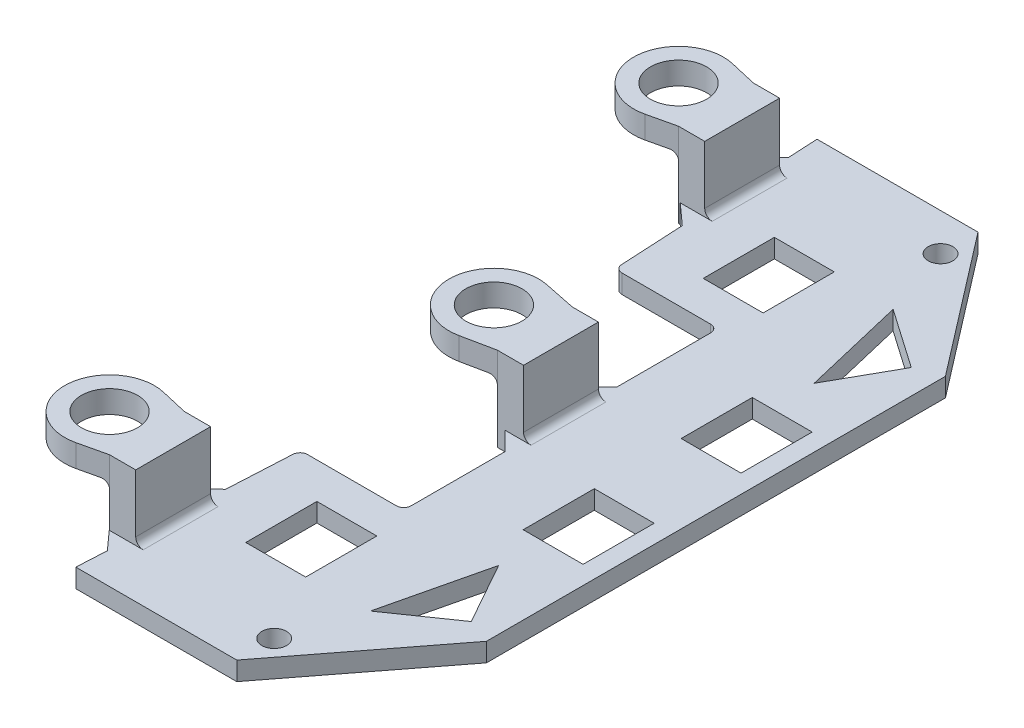
SolidWorks part; units mm, degrees
ref_plane "Plano frontal" through (0, 0, 0) normal (0, 0, 1) x (1, 0, 0)
ref_plane "Plano superior" through (0, 0, 0) normal (0, 1, 0) x (1, 0, 0)
ref_plane "Plano direito" through (0, 0, 0) normal (1, 0, 0) x (0, 0, -1)
sketch "Esboço1" plane through (0, 0, 0) normal (0, 1, 0) x (1, 0, 0)
  line L2 (-10.5, -21) -> (-10.5, 21) construction
  line L15 (-10.5, 21) -> (-10.5, -21)
  line L24 (-25.8, -49.5) -> (-4.3, -49.5)
  line L27 (-25.8, 49.5) -> (-4.3, 49.5)
  line L28 (-4.3, 49.5) -> (10.2, 30.65)
  line L29 (10.2, 30.65) -> (10.2, -30.65)
  line L30 (10.2, -30.65) -> (-4.3, -49.5)
  line L32 (-10.5, -21) -> (-24.3, -21)
  line L33 (-24.3, -21) -> (-25.8, -49.5)
  line L34 (-10.5, 21) -> (-24.3, 21)
  line L35 (-24.3, 21) -> (-25.8, 49.5)
  point P0 (0, 0)
  point P1 (0, 0)
  point P2 (0, 0)
  point P3 (-10.5, 0)
  dimension "D3" = 10.5
  dimension "D4" = 36
  dimension "D2" = 10.2
  dimension "D5" = 34.5
  dimension "D6" = 14.5
  dimension "D7" = 42
  dimension "D11" = 49.5
  dimension "D13" = 49.5
  dimension "D14" = 30.65
  dimension "D15" = 30.65
  dimension "D16" = 21.5
extrude "Ressalto-extrusão1" add sketch "Esboço1" along normal mid plane 2.5 contours L24 L30 L29 L28 L27 | L15 | L35 L34 L15 | L24 L30 L29 L28 L27 L35 L34 L15 L32 L33 region at (-6.3414, 0, 0)
sketch "Esboço8" plane through (0, 1.25, 0) normal (0, 1, 0) x (1, 0, 0)
  line L1 (-17.3, 25.8) -> (-9.3, 25.8)
  line L2 (-17.3, 25.8) -> (-17.3, 35.3)
  line L3 (-17.3, 35.3) -> (-9.3, 35.3)
  line L4 (-9.3, 25.8) -> (-9.3, 35.3)
  line L6 (-25.8, 49.5) -> (-4.3, 49.5) construction
  line L7 (10.2, 30.65) -> (10.2, -30.65) construction
  line L8 (-0.25, 5.8) -> (7.75, 5.8)
  line L9 (-0.25, 5.8) -> (-0.25, 15.3)
  line L10 (-0.25, 15.3) -> (7.75, 15.3)
  line L11 (7.75, 5.8) -> (7.75, 15.3)
  line L12 (-4.3, 49.5) -> (10.2, 30.65) construction
  line L13 (-4.3, 44.5) -> (-8.1462, 49.5) construction
  line L14 (-1.375, 0) -> (1.375, 0) construction
  circle A0 centre (-4.3, 44.5) radius 1.65
  point P6 (-13.3, 25.8)
  point P19 (-0.25, 10.55)
  point P23 (-17.3, 30.55)
  point P24 (3.75, 15.3)
  dimension "D8" = 3.3
  dimension "D1" = 8
  dimension "D2" = 9.5
  dimension "D3" = 23.7
  dimension "D4" = 23.5
  dimension "D5" = 15.3
  dimension "D6" = 2.45
  dimension "D7" = 3.0486
  dimension "D9" = 6.3082
  dimension "D10" = 14.5
  dimension "D11" = 5
  dimension "D12" = 10.55
  dimension "D13" = 30.55
  dimension "D14" = 6.45
extrude "Corte-extrusão6" cut sketch "Esboço8" against normal through all
sketch "Esboço9" plane through (0, 1.25, 0) normal (0, 1, 0) x (1, 0, 0)
  line L0 (6.9015, 29.3849) -> (-1.0461, 34.9078)
  line L1 (-1.0461, 34.9078) -> (2.2431, 21.0714)
  line L2 (2.2431, 21.0714) -> (6.9015, 29.3849)
  point P2 (-7.0972, -44.8275)
  point P4 (2.2431, 21.0714)
  point P5 (-1.0461, 34.9078)
  point P6 (-2.3014, -31.2953)
  point P7 (-1.2891, -41.9419)
  point P8 (-0.6864, -30.8137)
  point P9 (-2.4256, 37.7818)
  point P10 (6.9015, 29.3849)
  point P11 (2.6327, -36.8446)
extrude "Corte-extrusão5" cut sketch "Esboço9" against normal blind 10
sketch "Esboço12" plane through (0, 0, 0) normal (0, 1, 0) x (1, 0, 0)
  line L1 (-24.3, 43) -> (-27.8, 43)
  line L2 (-24.3, 43) -> (-24.3, 33)
  line L3 (-24.3, 33) -> (-27.8, 33)
  line L4 (-27.8, 43) -> (-27.8, 33)
  line L5 (10.2, 30.65) -> (10.2, -30.65) construction
  point P4 (-24.3, 38)
  point P6 (-26.05, 33)
  dimension "D2" = 3.5
  dimension "D1" = 38
  dimension "D3" = 10
  dimension "D4" = 36.25
extrude "Ressalto-extrusão4" add sketch "Esboço12" along normal blind 10 and the other way blind 1.25
sketch "Esboço13" plane through (0, 10, 0) normal (0, 1, 0) x (1, 0, 0)
  line L0 (-27.8, 43) -> (-27.8, 33) construction
  line L1 (10.2, 30.65) -> (10.2, -30.65) construction
  line L2 (-31.445, 43.845) -> (-27.8, 43)
  line L3 (-27.8, 43) -> (-27.8, 33)
  line L4 (-27.8, 33) -> (-31.445, 32.155)
  circle A0 centre (-32.8, 38) radius 6 construction
  arc A1 (-31.445, 43.845) -> (-31.445, 32.155) centre (-32.8, 38) ccw
  circle A2 centre (-32.8, 38) radius 3.75
  point P5 (-27.8, 38)
  point P13 (0, 0)
  line M4 (-27.8, 43) -> (-27.8, 33)
  dimension "D2" = 12
  dimension "D4" = 7.5
  dimension "D3" = 43
extrude "Ressalto-extrusão5" add sketch "Esboço13" against normal blind 3 contours L2 A1 L4 M4 region at (-29.6593, 10, -43.2639)
sketch "Esboço11" [suppressed] plane through (0, 0.9, 0) normal (0, 1, 0) x (1, 0, 0)
  circle A2 centre (-28.61, -38) radius 1.75
  circle A3 centre (-28.61, -38) radius 1.75 construction
  circle A4 centre (-28.61, -38) radius 2.5
  dimension "D1" = 5
extrude "Ressalto-extrusão3" [suppressed] add sketch "Esboço11" along normal blind 1.5
mirror "Espelhar1" about plane through (0, 0, 0) normal (0, 0, 1) of "Ressalto-extrusão5", "Ressalto-extrusão4", "Corte-extrusão6", "Corte-extrusão5"
sketch "Esboço14" plane through (0, -1.25, 0) normal (0, -1, 0) x (1, 0, 0)
  line L0 (1.375, 0) -> (-1.375, 0) construction
  line L1 (-10.5, -5) -> (-14, -5)
  line L2 (-10.5, -5) -> (-10.5, 5)
  line L3 (-10.5, 5) -> (-14, 5)
  line L4 (-14, -5) -> (-14, 5)
  line L5 (-10.5, -21) -> (-10.5, 21) construction
  point P4 (-10.5, 0)
  dimension "D1" = 10
  dimension "D2" = 3.5
extrude "Ressalto-extrusão6" add sketch "Esboço14" against normal up to surface (11.25 mm away) up to face at (-29.0742, 10, -38)
sketch "Esboço15" plane through (0, 10, 0) normal (0, 1, 0) x (1, 0, 0)
  line L1 (-18.2478, 5.8763) -> (-18.2478, -5.8763) construction
  line L3 (-1.375, 0) -> (1.375, 0) construction
  line L4 (10.2, 30.65) -> (10.2, -30.65) construction
  line L7 (-10.5, -5) -> (-10.5, 5) construction
  line L8 (-18.2478, 5.8763) -> (-14, 5)
  line L9 (-18.2478, -5.8763) -> (-14, -5)
  line L10 (-14, -5) -> (-14, 5)
  circle A0 centre (-19.46, 0) radius 3.75
  circle A1 centre (-19.46, 0) radius 6 construction
  arc A2 (-18.2478, 5.8763) -> (-18.2478, -5.8763) centre (-19.46, 0) ccw
  line M6 (-14, 5) -> (-14, -5)
  dimension "D1" = 7.5
  dimension "D2" = 12
  dimension "D3" = 29.66
  dimension "D4" = 8.96
extrude "Ressalto-extrusão7" add sketch "Esboço15" against normal blind 3 contours A2 A0 M6 region at (-16.1574, 10, -5.2756)
chamfer "Chanfro1" distance 2.5 angle 45 6 edges at (-10.5, 0, -5) (-10.5, 0, 5) (-25.4579, 0, 43) (-24.9316, 0, 33) (-25.4579, 0, -43) (-24.9316, 0, -33) first distance on face at (-12.25, 4.2917, -5) first distance on face at (-12.25, 4.2917, 5) first distance on face at (-25.6289, 0, 46.25) first distance on face at (-24.6158, 0, 27) first distance on face at (-25.6289, 0, -46.25) first distance on face at (-24.6158, 0, -27)
fillet "Filete1" radius 1 10 edges at (-27.8, 7, -38) (-14, 7, 0) (-27.8, 7, 38) (-24.3, 1.25, -38) (-10.5, 1.25, 0) (-24.3, 1.25, 38) (-24.3, 0, 21) (-10.5, 0, 21) (-10.5, 0, -21) (-24.3, 0, -21)
